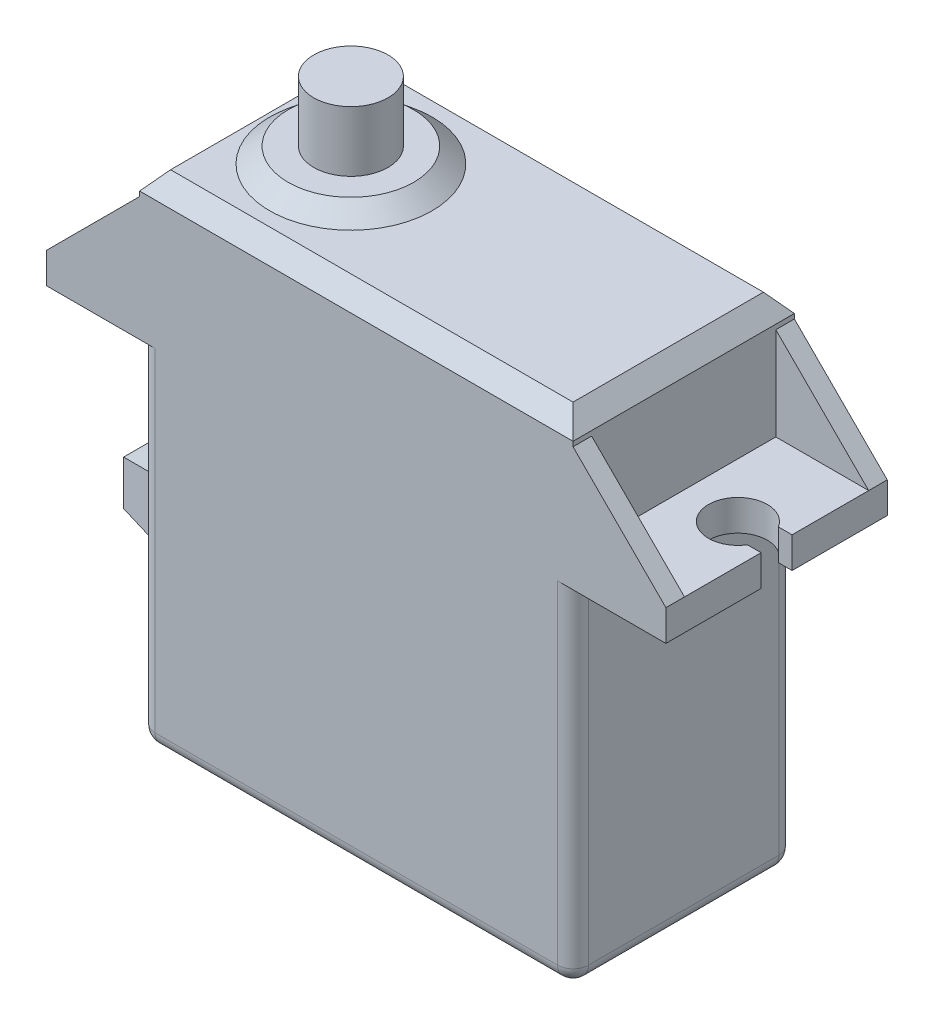
SolidWorks part; units mm, degrees
ref_plane "Plan de face" through (0, 0, 0) normal (0, 0, 1) x (1, 0, 0)
ref_plane "Plan de dessus" through (0, 0, 0) normal (0, 1, 0) x (1, 0, 0)
ref_plane "Plan de droite" through (0, 0, 0) normal (1, 0, 0) x (0, 0, -1)
sketch "Esquisse1" plane through (0, 0, 0) normal (0, 0, 1) x (1, 0, 0)
  line L1 (-14, -16) -> (14, -16)
  line L2 (-14, -16) -> (-14, 16)
  line L3 (-14, 16) -> (14, 16)
  line L4 (14, -16) -> (14, 16)
  line L5 (-14, -16) -> (14, 16) construction
  line L6 (-14, 16) -> (14, -16) construction
  point P0 (0, 0)
  dimension "D1" = 28
  dimension "D2" = 32
extrude "Boss.-Extru.1" add sketch "Esquisse1" along normal mid plane 14.3
sketch "Esquisse2" plane through (-14, 0, 0) normal (-1, 0, 0) x (0, 0, 1)
  line L0 (7.15, -16) -> (-7.15, -16) construction
  line L1 (5.95, 14.5) -> (7.15, 14.5)
  line L2 (-7.15, 14.5) -> (-7.15, 6.5)
  line L3 (-7.15, 6.5) -> (-5.3159, 6.5)
  line L4 (-5.95, 14.5) -> (-5.95, 8.5)
  line L6 (7.15, 14.5) -> (7.15, 6.5)
  line L7 (7.15, 6.5) -> (5.3665, 6.5)
  line L8 (5.95, 14.5) -> (5.95, 8.5)
  line L9 (5.3665, 6.5) -> (-5.3159, 6.5)
  line L10 (-7.15, 14.5) -> (-5.95, 14.5)
  line L11 (5.95, 8.5) -> (-5.95, 8.5)
  dimension "D1" = 22.5
  dimension "D2" = 2
  dimension "D3" = 1.2
  dimension "D4" = 1.2
  dimension "D5" = 6
extrude "Boss.-Extru.2" add sketch "Esquisse2" along normal blind 6
chamfer "Chanfrein1" distance 6 angle 45 2 edges at (-20, 14.5, 6.55) (-20, 14.5, -6.55)
sketch "Esquisse3" plane through (0, 8.5, 0) normal (0, 1, 0) x (1, 0, 0)
  line L0 (-20, -5.95) -> (-20, 5.95) construction
  line L1 (-20, 7.15) -> (-14, 7.15) construction
  line L2 (-20, 1) -> (-19.1155, 1)
  line L3 (-20, 1) -> (-20, -1)
  line L4 (-20, -1) -> (-19.1155, -1)
  arc A0 (-19.1155, -1) -> (-19.1155, 1) centre (-17.5, 0) ccw
  dimension "D1" = 3.8
  dimension "D2" = 2.5
  dimension "D3" = 2
  dimension "D4" = 1
  dimension "D5" = 7.15
extrude "Enlèv. mat.-Extru.1" cut sketch "Esquisse3" against normal blind 6
mirror "Symétrie1" about plane through (0, 0, 0) normal (1, 0, 0) of "Enlèv. mat.-Extru.1", "Chanfrein1", "Boss.-Extru.2"
fillet "Congé1" radius 1 8 edges at (-14, -16, 0) (0, -16, 7.15) (14, -16, 0) (0, -16, -7.15)
sketch "Esquisse4" plane through (0, 16, 0) normal (0, 1, 0) x (1, 0, 0)
  line L0 (-14, -7.15) -> (-14, 7.15) construction
  circle A0 centre (-7.5, 0) radius 5.25
  dimension "D1" = 10.5
  dimension "D2" = 6.5
extrude "Boss.-Extru.3" add sketch "Esquisse4" along normal blind 1
chamfer "Chanfrein2" distance 1 angle 50 1 edges at (-7.5, 17, 5.25) first distance on face at (-7.5, 17, 5.25)
sketch "Esquisse5" plane through (0, 17, 0) normal (0, 1, 0) x (1, 0, 0)
  circle A0 centre (-7.5, 0) radius 2.4
  dimension "D1" = 4.8
extrude "Boss.-Extru.4" add sketch "Esquisse5" along normal blind 3.9
chamfer "Chanfrein3" distance 1 angle 50 4 edges at (14, 16, 0) (0, 16, -7.15) (0, 16, 7.15) (-14, 16, 0) first distance on face at (-7.5, 16, -5.25)
sketch "Esquisse6" plane through (-14, 0, 0) normal (-1, 0, 0) x (0, 0, 1)
  line L0 (6.15, -16) -> (-6.15, -16) construction
  line L1 (3.2416, -9.5) -> (-4.2584, -9.5)
  line L2 (3.2416, -9.5) -> (3.2416, -4.5)
  line L3 (3.2416, -4.5) -> (-4.2584, -4.5)
  line L4 (-4.2584, -9.5) -> (-4.2584, -4.5)
  line L5 (3.2416, -9.5) -> (-4.2584, -4.5) construction
  line L6 (3.2416, -4.5) -> (-4.2584, -9.5) construction
  point P0 (-0.5084, -7)
  dimension "D1" = 7.5
  dimension "D2" = 5
  dimension "D3" = 6.5
extrude "Boss.-Extru.5" add sketch "Esquisse6" along normal blind 6
chamfer "Chanfrein4" distance 6 angle 10 4 edges at (-20, -7, -4.2584) (-20, -9.5, -0.5084) (-20, -7, 3.2416) (-20, -4.5, -0.5084) first distance on face at (-17, -7, -4.2584) first distance on face at (-17, -9.5, -0.5084) first distance on face at (-17, -7, 3.2416) first distance on face at (-17, -4.5, -0.5084)
